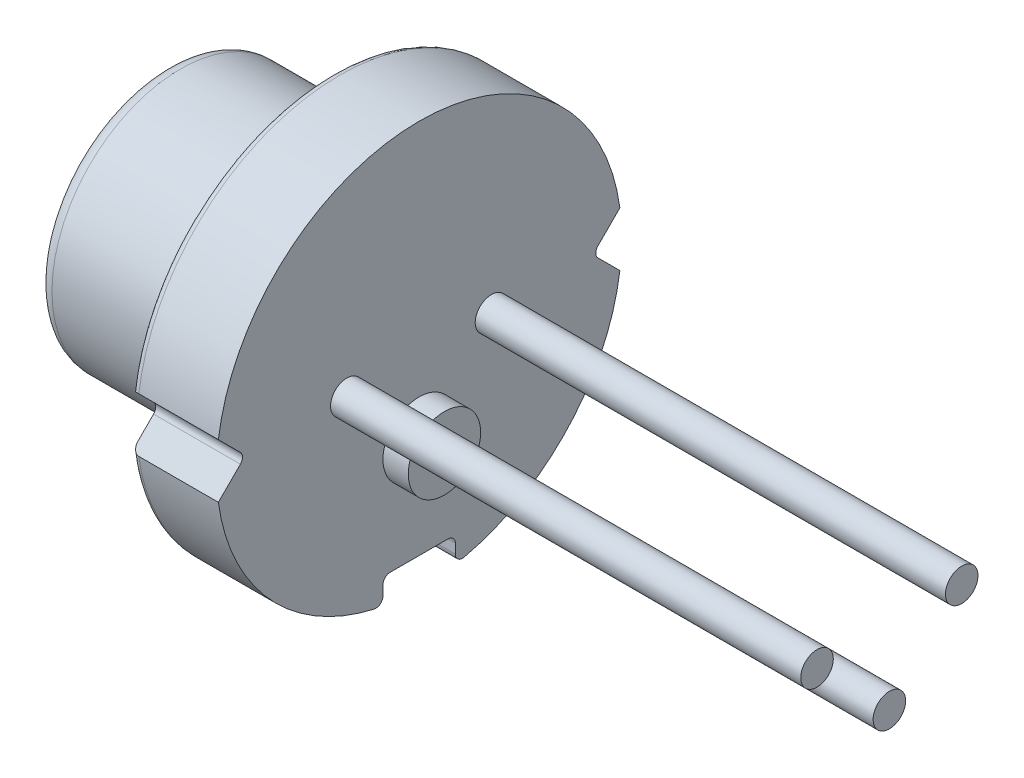
SolidWorks part; units mm, degrees
material "Brass"
ref_plane "Front Plane" through (0, 0, 0) normal (0, 0, 1) x (1, 0, 0)
ref_plane "Top Plane" through (0, 0, 0) normal (0, 1, 0) x (1, 0, 0)
ref_plane "Right Plane" through (0, 0, 0) normal (1, 0, 0) x (0, 0, -1)
sketch "Sketch4" plane through (0, 0, 0) normal (0, 0, 1) x (1, 0, 0)
  line L0 (0, 3.9054) -> (0, -4.2174) construction
  line L1 (-2.4917, 0) -> (5.581, 0) construction
  line L2 (0, 0) -> (0, 0.7)
  line L3 (-0.95, 0.8) -> (-0.65, 0.8)
  line L4 (2.55, 0) -> (2.55, 2.8)
  line L5 (0, 0) -> (2.55, 0)
  line L6 (-0.65, 0.8) -> (-0.65, 0.7)
  line L7 (-0.65, 0.7) -> (0, 0.7)
  line L8 (2.55, 2.8) -> (1.35, 2.8)
  line L9 (-0.95, 0.8) -> (-0.95, 1.775)
  line L11 (-0.95, 1.775) -> (0.8, 1.775)
  line L13 (1.35, 2.8) -> (1.35, 2.1)
  line L16 (1.35, 2.1) -> (1.05, 2.1)
  line L18 (1.05, 2.1) -> (1.05, 2.025)
  arc A0 (1.05, 2.025) -> (0.8, 1.775) centre (0.8, 2.025) cw
  dimension "D11" = 0.25
  dimension "D2" = 1.6
  dimension "D3" = 3.55
  dimension "D4" = 4.2
  dimension "D5" = 5.6
  dimension "D6" = 1.35
  dimension "D7" = 0.7
  dimension "D8" = 2.3
  dimension "D9" = 1.2
  dimension "D10" = 0.3
  dimension "D14" = 0.3
revolve "Revolve2" add sketch "Sketch4" angle 360 about L1
sketch "Sketch6" plane through (2.55, 0, 0) normal (1, 0, 0) x (0, 0, -1)
  line L0 (-5.8415, 0) -> (5.3793, 0) construction
  line L1 (0, 5.0519) -> (0, -5.1932) construction
  circle A0 centre (0, 0) radius 1 construction
  circle A1 centre (1, 0) radius 0.225
  circle A2 centre (0, -1) radius 0.225
  circle A3 centre (-1, 0) radius 0.225
  circle A4 centre (0, -1) radius 0.5
  dimension "D1" = 2
  dimension "D2" = 0.45
  dimension "D3" = 1
extrude "Extrude2" add sketch "Sketch6" along normal blind 6.5 contours A2 | A3 | A1 region at (2.55, 0, -1) region at (2.55, -1, 0) region at (2.55, 0, 1)
sketch "Sketch8" plane through (2.55, 0, 0) normal (1, 0, 0) x (0, 0, -1)
  line L0 (-4.3892, 0) -> (4.2829, 0) construction
  line L1 (0, 0) -> (0, 4.3747) construction
  line L2 (0, 0) -> (0, -2.8) construction
  line L3 (0, -2.8) -> (0.0051, -4.3895) construction
  line L4 (2.4, 0) -> (2.7748, 0.3748)
  line L5 (0.5, -3.2) -> (-0.5, -3.2)
  line L6 (0.5, -3.2) -> (0.5, -2.4)
  line L7 (0.5, -2.4) -> (-0.5, -2.4)
  line L8 (-0.5, -3.2) -> (-0.5, -2.4)
  line L9 (0.5, -3.2) -> (-0.5, -2.4) construction
  line L10 (0.5, -2.4) -> (-0.5, -3.2) construction
  line L11 (2.4, 0) -> (2.7748, -0.3748)
  line L12 (-2.4, 0) -> (-2.7748, -0.3748)
  line L13 (-2.4, 0) -> (-2.7748, 0.3748)
  circle A0 centre (0, 0) radius 2.8 construction
  point P6 (0, -2.8)
  circle M2 centre (0, 0) radius 2.8
  dimension "D4" = 2.4
  dimension "D1" = 1
  dimension "D2" = 0.8
  dimension "D3" = 90
extrude "Cut-Extrude1" cut sketch "Sketch8" against normal through all contours L12 L13 M2 | L4 L11 M2 | L8 L6 L7 M2 region at (2.55, 0, -2.661) region at (2.55, 0, 2.661) region at (2.55, -2.5928, 0)
sketch "Sketch10" plane through (-0.65, 0, 0) normal (-1, 0, 0) x (0, 0, 1)
  circle A0 centre (0, 0) radius 0.8
extrude "Boss-Extrude1" add sketch "Sketch10" along normal blind 0.25
fillet "Fillet1" radius 0.2 1 edges at (-0.95, 0, 1.775)
fillet "Fillet2" radius 0.1 3 edges at (1.35, -1.9346, -2.0242) (1.35, -1.9346, 2.0242) (1.35, 2.8, 0)
extrude "Boss-Extrude2" add sketch "Sketch6<3>" along normal blind 0.35 contours A4 A2 region at (2.55, -1, 0.4859)
sketch "Sketch6<3>" plane through (2.55, 0, 0) normal (1, 0, 0) x (0, 0, -1) same geometry as "Sketch6"
fillet "Fillet4" radius 0.1 1 edges at (1.95, -2.4, 0.5)
fillet "Fillet5" radius 0.1 1 edges at (1.95, -2.4, -0.5)
fillet "Fillet6" radius 0.1 9 edges at (2, -2.755, -0.5) (1.3726, -2.7177, -0.5) (1.35, -2.5766, -0.5) (1.35, -2.4293, -0.4707) (1.35, -2.4, 0) (1.35, -2.4293, 0.4707) (1.35, -2.5766, 0.5) (1.3883, -2.7333, 0.5) (2, -2.755, 0.5)
fillet "Fillet7" radius 0.1 1 edges at (1.95, 0, 2.4)
fillet "Fillet8" radius 0.1 1 edges at (1.95, 0, -2.4)
